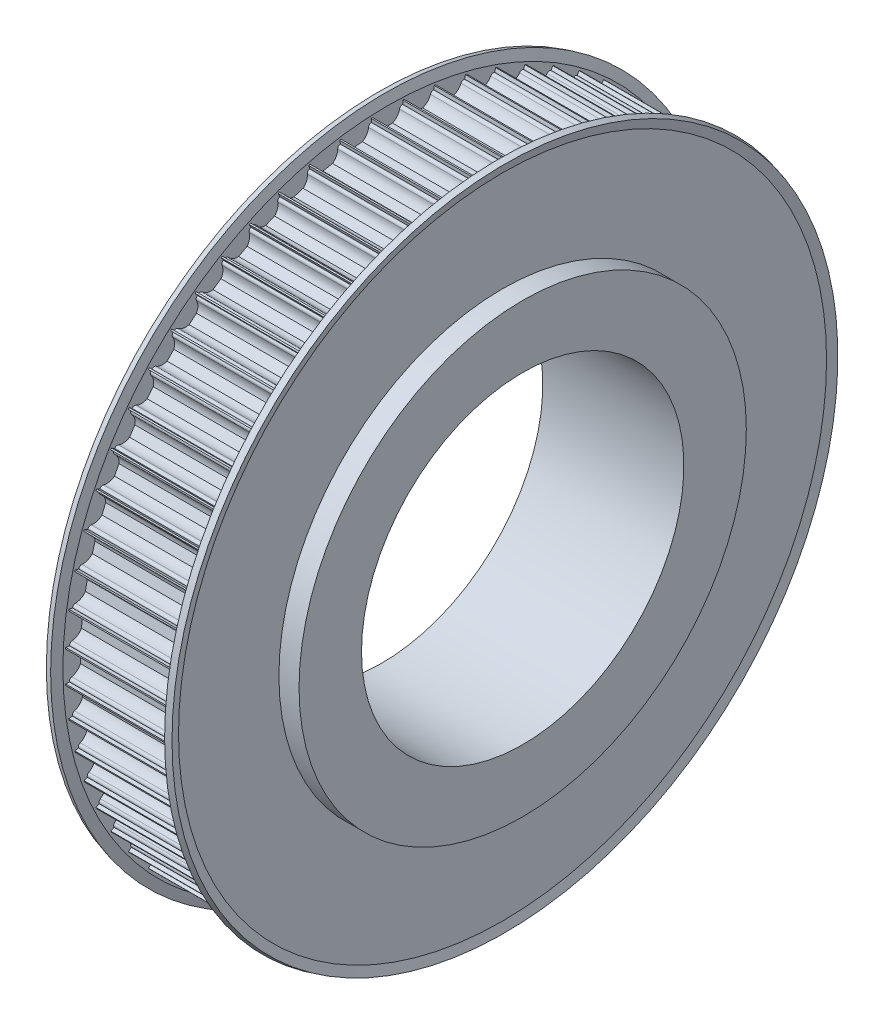
SolidWorks part; units mm, degrees
ref_plane "Front Plane" through (0, 0, 0) normal (0, 0, 1) x (1, 0, 0)
ref_plane "Top Plane" through (0, 0, 0) normal (0, 1, 0) x (1, 0, 0)
ref_plane "Right Plane" through (0, 0, 0) normal (1, 0, 0) x (0, 0, -1)
sketch "Sketch1" plane through (0, 0, 0) normal (0, 0, 1) x (1, 0, 0)
  line L0 (0, 0) -> (12.9639, 0) construction
  line L1 (0, 80) -> (0, 40)
  line L2 (0, 40) -> (35, 40)
  line L3 (35, 40) -> (35, 55.5)
  line L4 (35, 55.5) -> (30, 55.5)
  line L5 (30, 55.5) -> (30, 80)
  line L6 (30, 80) -> (0, 80)
  dimension "D1" = 80
  dimension "D2" = 40
  dimension "D3" = 15.5
  dimension "D4" = 5
  dimension "D5" = 30
revolve "Revolve1" add sketch "Sketch1" angle 360 about L0
sketch "Sketch2" plane through (0, 0, 0) normal (-1, 0, 0) x (0, 0, 1)
  line L0 (-3.6742, 79) -> (-3.75, 79)
  line L1 (-3.75, 79) -> (-3.75, 81)
  line L2 (-3.75, 81) -> (3.75, 81)
  line L3 (3.75, 81) -> (3.75, 79)
  line L4 (3.75, 79) -> (3.6742, 79)
  line L5 (-1.199, 76.25) -> (1.199, 76.25)
  arc A0 (2.9394, 78.4) -> (1.199, 76.25) centre (0, 79) cw
  arc A2 (2.9394, 78.4) -> (3.6742, 79) centre (3.6742, 78.25) cw
  arc A3 (-2.9394, 78.4) -> (-3.6742, 79) centre (-3.6742, 78.25) ccw
  arc A4 (-1.199, 76.25) -> (-2.9394, 78.4) centre (0, 79) cw
  point P3 (0, 81)
  point P11 (3, 79)
  point P14 (-3, 79)
  dimension "D2" = 3
  dimension "D5" = 0.75
  dimension "D1" = 79
  dimension "D3" = 7.5
  dimension "D4" = 2
  dimension "D6" = 2.75
extrude "Cut-Extrude1" cut sketch "Sketch2" against normal through all
pattern_circular "CirPattern1" count 64 over 360 about axis through (0, 0, 0) along (-1, 0, 0) of "Cut-Extrude1"
sketch "Sketch3" plane through (0, 0, 0) normal (0, 0, 1) x (1, 0, 0)
  line L0 (30, 55.5) -> (28.5, 55.5)
  line L1 (28.5, 55.5) -> (28.5, 80.61)
  line L2 (28.5, 80.61) -> (29.1431, 83.01)
  line L3 (29.1431, 83.01) -> (30.592, 82.6218)
  line L4 (30.592, 82.6218) -> (30, 80.4125)
  line L5 (30, 80.4125) -> (30, 55.5)
  line L6 (35, 55.5) -> (30, 55.5) construction
  line L7 (17.5, 15.4656) -> (17.5, 10.5856) construction
  line L8 (0, 15.4656) -> (35, 15.4656) construction
  line L15 (15, 79.8948) -> (15, 52.0086) construction
  line L16 (0, 79.8948) -> (30, 79.8948) construction
  line L17 (30, 52.0086) -> (0, 52.0086) construction
  line L18 (0, 55.5) -> (1.5, 55.5)
  line L19 (0, 80.4125) -> (0, 55.5)
  line L20 (1.5, 55.5) -> (1.5, 80.61)
  line L21 (1.5, 80.61) -> (0.8569, 83.01)
  line L22 (-0.592, 82.6218) -> (0, 80.4125)
  line L23 (0.8569, 83.01) -> (-0.592, 82.6218)
  dimension "D1" = 15
  dimension "D2" = 2.4
  dimension "D3" = 1.5
  dimension "D4" = 25.11
revolve "Revolve2" add sketch "Sketch3" angle 360 about L0
